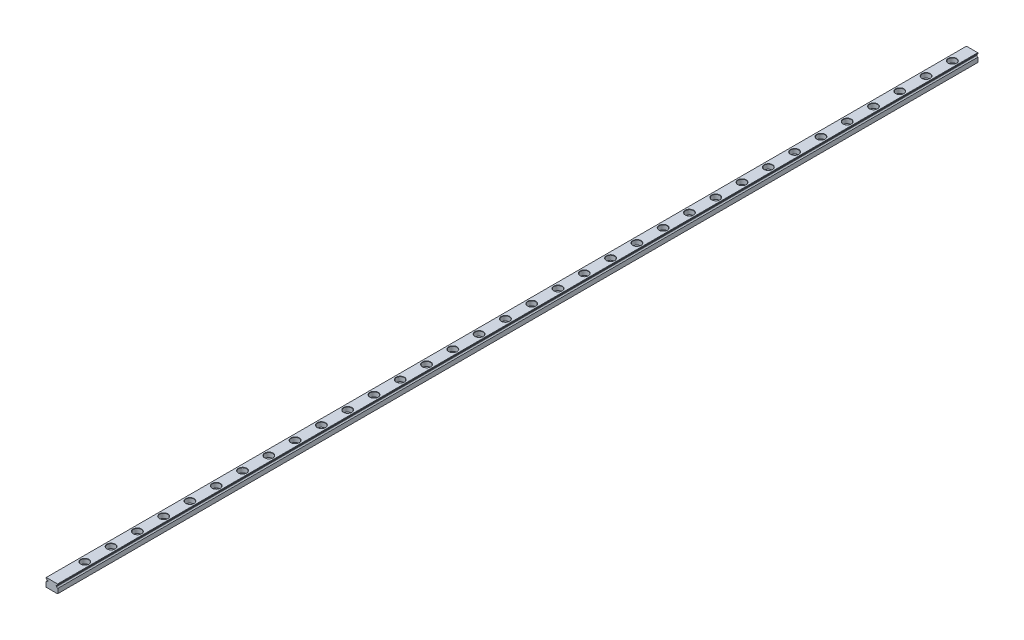
SolidWorks part; units mm, degrees
ref_plane "Спереди" through (0, 0, 0) normal (0, 0, 1) x (1, 0, 0)
ref_plane "Сверху" through (0, 0, 0) normal (0, 1, 0) x (1, 0, 0)
ref_plane "Справа" through (0, 0, 0) normal (1, 0, 0) x (0, 0, -1)
sketch "Sketch1" plane through (0, 0, 0) normal (0, 0, 1) x (1, 0, 0)
  line L0 (0, 0) -> (0, 4.3706) construction
  line L1 (-4.3, -3.25) -> (4.3, -3.25)
  line L2 (-4.5, -3.05) -> (-4.5, 0.455)
  line L3 (-4.3, 3.25) -> (4.3, 3.25)
  line L4 (4.5, -3.05) -> (4.5, 0.455)
  line L5 (-4.5, -3.25) -> (4.5, 3.25) construction
  line L6 (-4.5, 3.25) -> (4.5, -3.25) construction
  line L7 (-4.5, 2.445) -> (-4.5, 3.05)
  line L8 (4.5, 2.445) -> (4.5, 3.05)
  line L9 (-4.5, -3.05) -> (-4.3, -3.25)
  line L10 (4.3, -3.25) -> (4.5, -3.05)
  line L11 (4.3, 3.25) -> (4.5, 3.05)
  line L12 (-4.5, 3.05) -> (-4.3, 3.25)
  line L13 (3.6177, 1.2625) -> (3.1501, 1.2625)
  line L14 (-3.6177, 1.2625) -> (-3.1501, 1.2625)
  line L15 (3.1501, 1.2625) -> (3.1501, 1.7625)
  line L16 (-3.6501, 1.7625) -> (-3.1501, 1.7625)
  line L17 (-3.1501, 1.2625) -> (-3.1501, 1.7625)
  line L18 (3.6501, 1.7625) -> (3.1501, 1.7625)
  arc A0 (-4.5, 2.445) -> (-3.6501, 1.7625) centre (-4.6, 1.45) cw
  arc A1 (4.5, 2.445) -> (3.6501, 1.7625) centre (4.6, 1.45) ccw
  arc A2 (-3.6177, 1.2625) -> (-4.5, 0.455) centre (-4.6, 1.45) cw
  arc A3 (3.6177, 1.2625) -> (4.5, 0.455) centre (4.6, 1.45) ccw
  point P0 (0, 0)
  dimension "D4" = 1
  dimension "D5" = 0.1
  dimension "D1" = 9
  dimension "D2" = 6.5
  dimension "D3" = 1.8
  dimension "D6" = 0.5
  dimension "D7" = 0.5
extrude "Extrude1" add sketch "Sketch1" along normal blind 700
sketch "Sketch2" plane through (0, 3.25, 0) normal (0, 1, 0) x (1, 0, 0)
  line L0 (0, 0) -> (0, -15) construction
  circle A0 centre (0, -15) radius 1.75
  circle A1 centre (0, -15) radius 3
  dimension "D1" = 3.5
  dimension "D2" = 6
  dimension "D3" = 15
extrude "Extrude2" cut sketch "Sketch2" against normal up to next contours A0 region at (0, 3.25, 15)
extrude "Extrude4" cut sketch "Sketch" against normal blind 3.5
sketch "Sketch" plane through (0, 3.25, 0) normal (0, 1, 0) x (1, 0, 0) same geometry as "Sketch2"
chamfer "Chamfer1" distance 0.2 angle 45 2 edges at (0, -3.25, 16.75) (0, 3.25, 18)
pattern_linear "LPattern1" count 34 spacing 20 along (0, 0, 1) of "Extrude4", "Chamfer1", "Extrude2"
